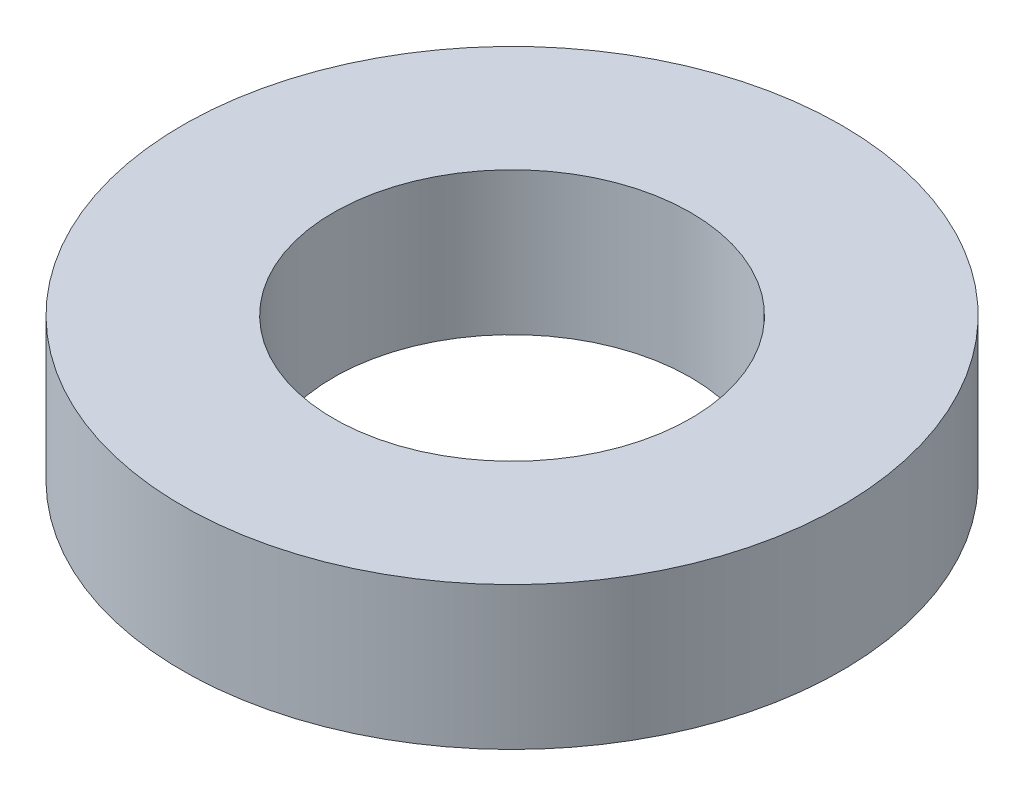
SolidWorks part; units mm, degrees
ref_plane "Front Plane" through (0, 0, 0) normal (0, 0, 1) x (1, 0, 0)
ref_plane "Top Plane" through (0, 0, 0) normal (0, 1, 0) x (1, 0, 0)
ref_plane "Right Plane" through (0, 0, 0) normal (1, 0, 0) x (0, 0, -1)
sketch "Sketch1" plane through (0, 0, 0) normal (0, 1, 0) x (1, 0, 0)
  circle A0 centre (0, 0) radius 60
  dimension "FLANGE_OD" = 120
extrude "Boss-Extrude1" add sketch "Sketch1" along normal blind 26
sketch "Sketch2" plane through (0, 0, 0) normal (0, 1, 0) x (1, 0, 0)
  circle A0 centre (0, 0) radius 32.5
  dimension "BORE_D" = 65
extrude "Cut-Extrude1" cut sketch "Sketch2" along normal through all
sketch "Sketch3" plane through (0, 26, 0) normal (0, 1, 0) x (1, 0, 0)
  circle A0 centre (0, 0) radius 20.3418 construction
  circle A1 centre (-20.3418, 0) radius 3.322
  dimension "BOLT_D" = 6.6439
  dimension "BOLT_PCD" = 40.6836
extrude "Cut-Extrude2" cut sketch "Sketch3" against normal blind 19.1505 rebuild error yes
pattern_circular "CirPattern1" count 6 over 360 rebuild error yes
